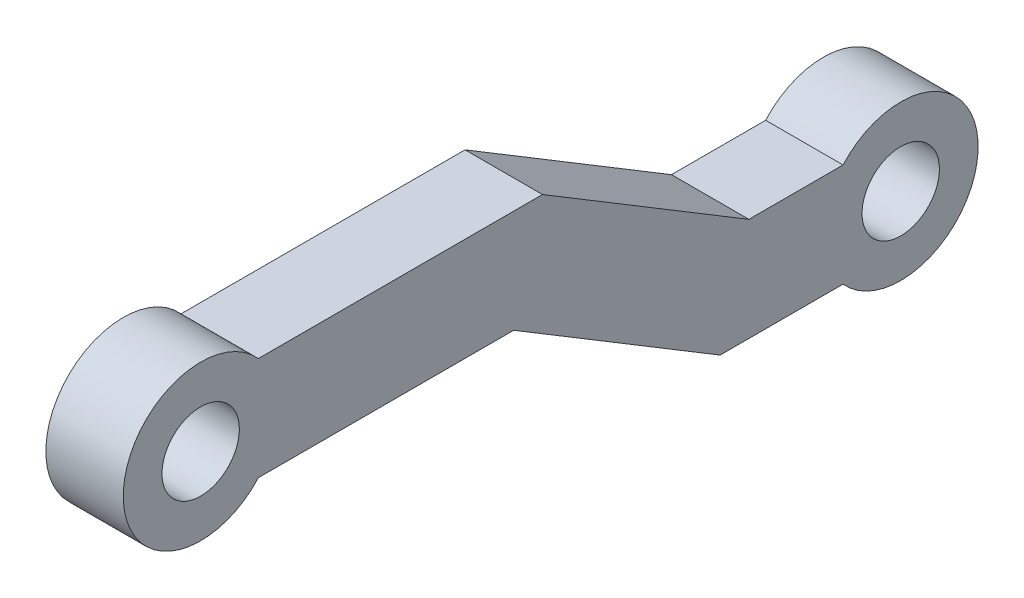
SolidWorks part; units mm, degrees
material "Plain Carbon Steel"
ref_plane "Front Plane" through (0, 0, 0) normal (0, 0, 1) x (1, 0, 0)
ref_plane "Top Plane" through (0, 0, 0) normal (0, 1, 0) x (1, 0, 0)
ref_plane "Right Plane" through (0, 0, 0) normal (1, 0, 0) x (0, 0, -1)
sketch "Sketch2" plane through (0, 0, 0) normal (1, 0, 0) x (0, 0, -1)
  line L16 (2.2361, 2) -> (13.2474, 2)
  line L17 (13.2474, 2) -> (21.2474, -2.8331)
  line L18 (21.2474, -2.8331) -> (24.8968, -2.8331)
  line L19 (0, 0) -> (27.1329, -4.8331) construction
  line L26 (2.2361, -2) -> (12.1329, -2)
  line L27 (12.1329, -2) -> (20.1329, -6.8331)
  line L28 (20.1329, -6.8331) -> (24.8968, -6.8331)
  line L29 (7.7417, 2) -> (7.7417, -2) construction
  line L30 (23.0721, -2.8331) -> (23.0721, -6.8331) construction
  circle A8 centre (0, 0) radius 1.5
  circle A9 centre (27.1329, -4.8331) radius 1.5
  circle A12 centre (0, 0) radius 3
  circle A13 centre (27.1329, -4.8331) radius 3
  point P9 (23.0721, -4.8331)
  point P14 (7.7417, 0)
  dimension "D1" = 10.1
  dimension "D5" = 3
  dimension "D7" = 4
  dimension "D8" = 7
  dimension "D3" = 6
  dimension "D4" = 4
  dimension "D2" = 27.56
  dimension "D6" = 4
  dimension "D9" = 15
extrude "Boss-Extrude1" add sketch "Sketch2" along normal blind 3 contours A13 L18 L17 L16 A12 L26 L27 L28 | A12 | A13 | A8 | A9 region at (0, -1.759, -13.7497)
